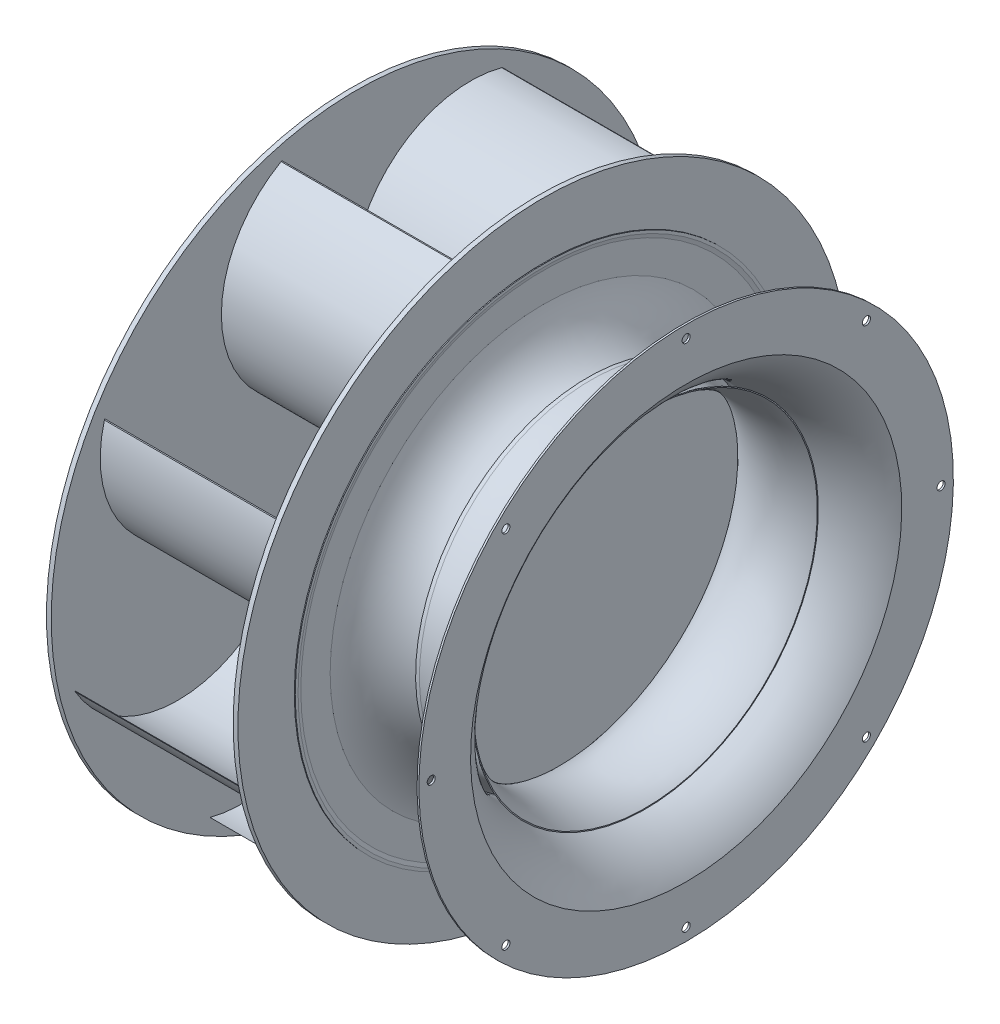
SolidWorks part; units mm, degrees
ref_plane "Front Plane" through (0, 0, 0) normal (0, 0, 1) x (1, 0, 0)
ref_plane "Top Plane" through (0, 0, 0) normal (0, 1, 0) x (1, 0, 0)
ref_plane "Right Plane" through (0, 0, 0) normal (1, 0, 0) x (0, 0, -1)
sketch "Sketch1" plane through (0, 0, 0) normal (0, 0, 1) x (1, 0, 0)
  line L0 (0, 0) -> (831.9083, 0) construction
  line L1 (0, 0) -> (0, 109)
  line L2 (5, 114) -> (70, 114)
  line L3 (70, 114) -> (70, 138)
  line L4 (70, 138) -> (90, 138)
  line L5 (90, 138) -> (90, 98)
  line L6 (90, 98) -> (95, 98)
  line L7 (95, 98) -> (95, 133)
  line L8 (95, 133) -> (105, 133)
  line L9 (105, 133) -> (105, 98)
  line L10 (105, 98) -> (129, 98)
  line L11 (129, 98) -> (129, 0)
  line L12 (129, 0) -> (0, 0)
  arc A0 (5, 114) -> (0, 109) centre (5, 109) ccw
  point P16 (0, 114)
  dimension "D10" = 5
  dimension "D1" = 114
  dimension "D2" = 24
  dimension "D3" = 70
  dimension "D4" = 40
  dimension "D5" = 35
  dimension "D6" = 5
  dimension "D7" = 20
  dimension "D8" = 10
  dimension "D9" = 59
revolve "Revolve1" add sketch "Sketch1" angle 360 about L0
sketch "Sketch2" plane through (129, 0, 0) normal (1, 0, 0) x (0, 0, -1)
  circle A0 centre (0, 0) radius 322
  dimension "D1" = 644
extrude "Extrude1" add sketch "Sketch2" along normal blind 5
sketch "Sketch9" plane through (129, 0, 0) normal (-1, 0, 0) x (0, 0, 1)
  circle A0 centre (0, 0) radius 317
  circle A1 centre (0, 0) radius 100
  circle A2 centre (0, 0) radius 322 construction
  dimension "D1" = 5
  dimension "D2" = 200
extrude "Extrude7" cut sketch "Sketch9" against normal blind 3
ref_plane "Plane1" through (326, 0, 0) normal (1, 0, 0) x (0, 0, -1)
sketch "Sketch3" plane through (326, 0, 0) normal (1, 0, 0) x (0, 0, -1)
  circle A0 centre (0, 0) radius 322
  dimension "D1" = 644
extrude "Extrude2" add sketch "Sketch3" along normal blind 5 separate body
sketch "Sketch4" plane through (134, 0, 0) normal (1, 0, 0) x (0, 0, -1)
  line L0 (0, 0) -> (0, 307) construction
  line L1 (0, 0) -> (161, 278.8602) construction
  line L2 (0, 112.5) -> (0.866, 112)
  line L3 (153.5, 265.8698) -> (154.366, 265.3698)
  circle A0 centre (0, 0) radius 307 construction
  circle A1 centre (0, 0) radius 322 construction
  circle A2 centre (0, 0) radius 112.5 construction
  arc A3 (0, 112.5) -> (153.5, 265.8698) centre (120.6282, 145.2694) cw
  arc A4 (0.866, 112) -> (154.366, 265.3698) centre (121.4942, 144.7694) cw
  dimension "D1" = 15
  dimension "D2" = 225
  dimension "D6" = 125
  dimension "D7" = 125
  dimension "D3" = 30
  dimension "D4" = 60
  dimension "D5" = 1
extrude "Extrude3" add sketch "Sketch4" along normal up to surface (197 mm away) up to face at (331, 0, -322)
ref_axis "Axis1" through (253.5503, 0, 0) along (-1, 0, 0)
pattern_circular "CirPattern1" count 8 over 360 about axis through (253.5503, 0, 0) along (-1, 0, 0) of "Extrude3"
sketch "Sketch5" plane through (0, 0, 0) normal (0, 0, 1) x (1, 0, 0)
  line L0 (0, 0) -> (527.2916, 0) construction
  line L1 (253.5503, 0) -> (75.411, 0) construction
  line L2 (331, 262.5) -> (332, 262.5)
  line L3 (332, 262.5) -> (332, 259.5)
  line L4 (331, 262.5) -> (331, 259.5)
  line L5 (439, 182.5) -> (439, 181.5)
  line L6 (70, 138) -> (70, -138) construction
  line L7 (331, -322) -> (331, 322) construction
  arc A0 (332, 259.5) -> (439, 182.5) centre (399.2668, 240.1305) ccw
  arc A1 (331, 259.5) -> (439, 181.5) centre (397.5983, 237.9437) ccw
  dimension "D7" = 70
  dimension "D8" = 70
  dimension "D1" = 181.5
  dimension "D2" = 1
  dimension "D3" = 1
  dimension "D4" = 3
  dimension "D5" = 262.5
  dimension "D6" = 369
revolve "Revolve2" add sketch "Sketch5" angle 360 about L0
ref_plane "Plane3" through (482, 0, 0) normal (1, 0, 0) x (0, 0, -1)
sketch "Sketch6" plane through (0, 0, 0) normal (0, 0, 1) x (1, 0, 0)
  line L0 (482, 282) -> (480, 282)
  line L1 (482, -251.35) -> (482, 251.35) construction
  line L2 (480, 282) -> (480, 227.5)
  line L3 (0, 0) -> (615.1417, 0) construction
  line L4 (0, 114) -> (0, -114) construction
  line L5 (253.5503, 0) -> (75.411, 0) construction
  line L6 (482, 282) -> (482, 227.5)
  line L7 (378, 181.5) -> (382, 181.5)
  line L8 (378, 181.5) -> (378, 179.5)
  line L9 (378, 179.5) -> (382, 179.5)
  arc A0 (382, 181.5) -> (480, 227.5) centre (395.2724, 280.6153) ccw
  arc A1 (382, 179.5) -> (482, 227.5) centre (395.9922, 278.5163) ccw
  dimension "D7" = 100
  dimension "D8" = 100
  dimension "D1" = 282
  dimension "D2" = 2
  dimension "D3" = 227.5
  dimension "D4" = 104
  dimension "D5" = 181.5
  dimension "D6" = 4
revolve "Revolve3" add sketch "Sketch6" angle 360 about L3
sketch "Sketch7" plane through (482, 0, 0) normal (1, 0, 0) x (0, 0, -1)
  line L0 (0, 0) -> (0, 269) construction
  circle A0 centre (0, 0) radius 269 construction
  circle A1 centre (0, 269) radius 4.25
  dimension "D1" = 538
  dimension "D2" = 8.5
extrude "Extrude5" cut sketch "Sketch7" against normal blind 5
pattern_circular "CirPattern2" count 8 over 360 about axis through (253.5503, 0, 0) along (-1, 0, 0) of "Extrude5"
sketch "Sketch8" plane through (0, 0, 0) normal (1, 0, 0) x (0, 0, -1)
  line L0 (0, 0) -> (0, 126) construction
  circle A0 centre (0, 0) radius 126 construction
  circle A1 centre (0, 126) radius 5
  dimension "D1" = 252
  dimension "D2" = 10
extrude "Extrude6" cut sketch "Sketch8" along normal up to surface (90 mm away) up to face at (90, 0, 138)
pattern_circular "CirPattern3" count 8 over 360 about axis through (253.5503, 0, 0) along (-1, 0, 0) of "Extrude6"
